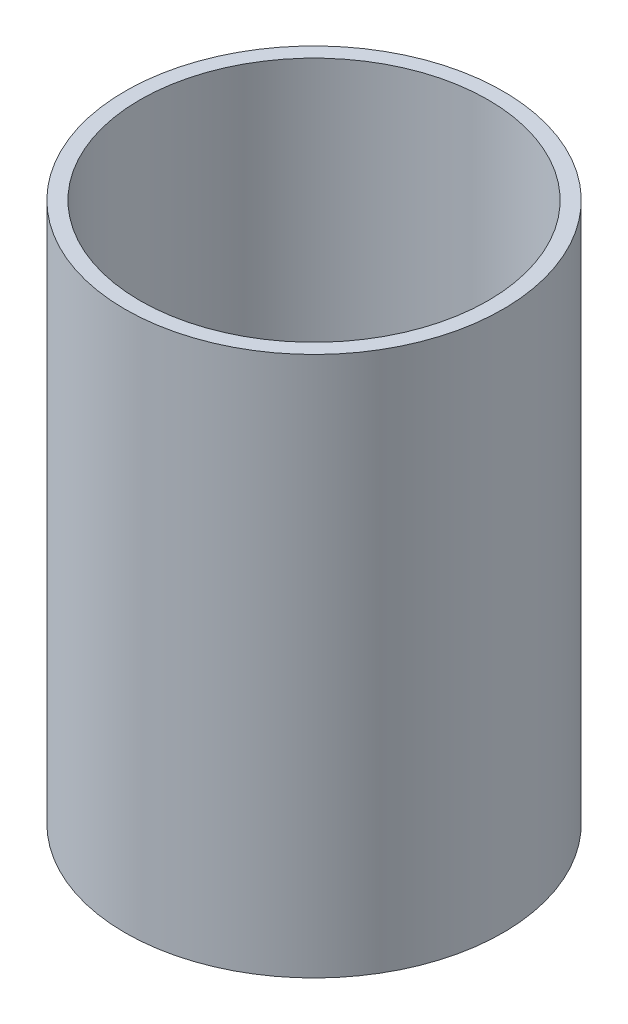
SolidWorks part; units mm, degrees
ref_plane "Front Plane" through (0, 0, 0) normal (0, 0, 1) x (1, 0, 0)
ref_plane "Top Plane" through (0, 0, 0) normal (0, 1, 0) x (1, 0, 0)
ref_plane "Right Plane" through (0, 0, 0) normal (1, 0, 0) x (0, 0, -1)
sketch "Sketch1" plane through (0, 0, 0) normal (0, 1, 0) x (1, 0, 0)
  circle A0 centre (0, 0) radius 19
  circle A1 centre (0, 0) radius 17.5
  dimension "D1" = 1.5
  dimension "D2" = 38
extrude "Boss-Extrude1" add sketch "Sketch1" along normal blind 52.3
extrude "Ressalto-extrusão1" add sketch "Sketch1<2>" against normal blind 2 contours A0
sketch "Sketch1<2>" plane through (0, 0, 0) normal (0, 1, 0) x (1, 0, 0) same geometry as "Sketch1"
